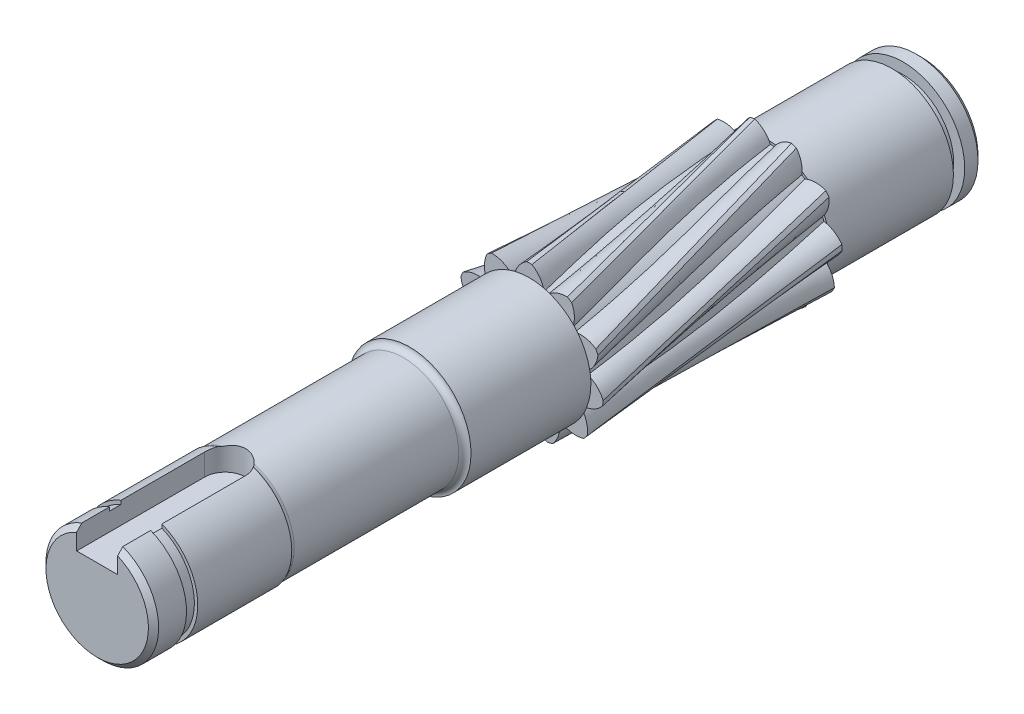
SolidWorks part; units mm, degrees
ref_plane "Plan de face" through (0, 0, 0) normal (0, 0, 1) x (1, 0, 0)
ref_plane "Plan de dessus" through (0, 0, 0) normal (0, 1, 0) x (1, 0, 0)
ref_plane "Plan de droite" through (0, 0, 0) normal (1, 0, 0) x (0, 0, -1)
sketch "Esquisse5" plane through (0, 0, 0) normal (0, 0, 1) x (1, 0, 0)
  circle A0 centre (0, 0) radius 5.75
  dimension "D1" = 11.5
extrude "Extrusion1" add sketch "Esquisse5" against normal blind 23.3
sketch "Esquisse1" plane through (0, 0, 0) normal (0, 0, 1) x (1, 0, 0)
  line L0 (0, 8.3971) -> (0, -8.0185) construction
  line L1 (-0.25, 7.2457) -> (0, 0) construction
  line L2 (0, 0) -> (0.25, 7.2457) construction
  line L3 (1.45, 5.5642) -> (0, 0) construction
  line L4 (0, 0) -> (-1.45, 5.5642) construction
  circle A0 centre (0, 0) radius 5.75 construction
  circle A1 centre (0, 0) radius 7.25 construction
  arc A2 (-0.25, 7.2457) -> (0.25, 7.2457) centre (0, 0) cw
  arc A3 (-1.45, 5.5642) -> (1.45, 5.5642) centre (0, 0) cw
  arc A4 (-1.45, 5.5642) -> (-0.25, 7.2457) centre (1.1069, 5.0084) cw
  arc A5 (1.45, 5.5642) -> (0.25, 7.2457) centre (-1.1069, 5.0084) ccw
  circle A6 centre (0, 0) radius 5.75 construction
  dimension "D1" = 0.5
  dimension "D2" = 14.5
  dimension "D4" = 1.5
  dimension "D5" = 2.6166
  dimension "D3" = 2.9
  dimension "angle1" = 3.952
  dimension "angle2" = 29.212
sketch "Esquisse6" plane through (0, 0, -23.3) normal (0, 0, -1) x (-1, 0, 0)
  line L0 (0, 0) -> (6.6208, 6.6208) construction
  line L1 (0, 8.3971) -> (0, -8.0185) construction
  line L2 (0, 0) -> (4.9467, 5.3003) construction
  line L3 (0, 0) -> (5.3003, 4.9467) construction
  line L4 (0, 0) -> (2.9092, 4.9598) construction
  line L5 (0, 0) -> (4.9598, 2.9092) construction
  arc A0 (5.3003, 4.9467) -> (4.9467, 5.3003) centre (0, 0) ccw
  arc A1 (0.25, 7.2457) -> (-0.25, 7.2457) centre (0, 0) ccw construction
  circle A2 centre (0, 0) radius 7.25 construction
  arc A3 (2.9092, 4.9598) -> (4.9467, 5.3003) centre (4.3242, 2.7588) cw
  arc A4 (-0.25, 7.2457) -> (-1.45, 5.5642) centre (1.1069, 5.0084) ccw construction
  arc A5 (4.9598, 2.9092) -> (5.3003, 4.9467) centre (2.7588, 4.3242) ccw
  arc A6 (4.9598, 2.9092) -> (2.9092, 4.9598) centre (0, 0) ccw
  circle A7 centre (0, 0) radius 5.75 construction
  dimension "D1" = 45
loft "Lissage3" add profiles "Esquisse1", "Esquisse6" connector at (1.45, 5.5642, 0) connector at (-2.9092, 4.9598, -23.3)
pattern_circular "Répétition circulaire2" count 11 over 360 about axis through (0, 0, -23.3) along (0, 0, 1) of "Lissage3" reverse direction yes
sketch "Esquisse7" plane through (0, 0, 0) normal (1, 0, 0) x (0, 0, -1)
  line L0 (-54.4054, 0) -> (40.026, 0) construction
  line L1 (23.3, 0) -> (0, 0) construction
  line L2 (-42.2, 0) -> (-42.2, 5)
  line L3 (23.3, 4.7066) -> (23.3, 6.7015) construction
  line L4 (38.3, 5.5) -> (38.3, 0)
  line L5 (37.8, 6) -> (36.5, 6)
  line L6 (36.5, 6) -> (36.5, 4.92)
  line L7 (36.5, 4.92) -> (35.4, 4.92)
  line L8 (35.4, 4.92) -> (35.4, 6)
  line L9 (35.4, 6) -> (23.3, 6)
  line L10 (23.3, 2.1737) -> (23.3, 4.142) construction
  line L11 (38.3, 5.5) -> (37.8, 6)
  line L12 (0, 6) -> (-11.7, 6)
  line L13 (0, 5.9603) -> (0, 3.8969) construction
  line L14 (-12.3, 5.4) -> (-28.3683, 5.4)
  line L15 (-28.7, 5.5) -> (-37.88, 5.5)
  line L16 (-37.88, 5.5) -> (-37.88, 5.17)
  line L17 (-37.88, 5.17) -> (-38.98, 5.17)
  line L18 (-38.98, 5.17) -> (-38.98, 5.5)
  line L19 (-38.98, 5.5) -> (-41.7, 5.5)
  line L20 (-41.7, 5.5) -> (-42.2, 5)
  line L21 (-42.2, 0) -> (0, 0)
  line L22 (0, 0) -> (0, 6)
  line L23 (23.3, 6) -> (23.3, 0)
  line L24 (23.3, 0) -> (38.3, 0)
  arc A0 (-11.7, 6) -> (-12.3, 5.4) centre (-12.3, 6) cw
  arc A1 (-28.3683, 5.4) -> (-28.7, 5.5) centre (-28.3683, 6) cw
  point P8 (38.3, 6)
  point P35 (-42.2, 5.5)
  dimension "D8" = 0.6
  dimension "D1" = 80.5
  dimension "D2" = 15
  dimension "D3" = 12
  dimension "D4" = 1.8
  dimension "D5" = 1.1
  dimension "D6" = 9.84
  dimension "D10" = 0.5
  dimension "D7" = 11.7
  dimension "D9" = 11
  dimension "D11" = 4.32
  dimension "D12" = 1.1
  dimension "D13" = 10.34
  dimension "D16" = 0.5
  dimension "D14" = 13.5
revolve "Révolution1" add sketch "Esquisse7" angle 360 about L0
ref_plane "Plan2" through (0, 5.5, 33.29) normal (0, 1, 0) x (-1, 0, 0)
sketch "Esquisse8" plane through (0, 5.5, 33.29) normal (0, 1, 0) x (-1, 0, 0)
  line L0 (-2, 8.91) -> (-2, -3.59)
  line L1 (5, 8.91) -> (-5, 8.91) construction
  line L2 (2, -3.59) -> (2, 8.91)
  line L3 (2, 8.91) -> (-2, 8.91)
  line L4 (0, 10.2561) -> (0, -4.5403) construction
  line L5 (0, 21.1154) -> (0, -73.316) construction
  arc A0 (-2, -3.59) -> (2, -3.59) centre (0, -3.59) ccw
  dimension "D1" = 4
  dimension "D2" = 12.5
extrude "Enlèv. mat.-Extru.1" cut sketch "Esquisse8" against normal blind 2.5
